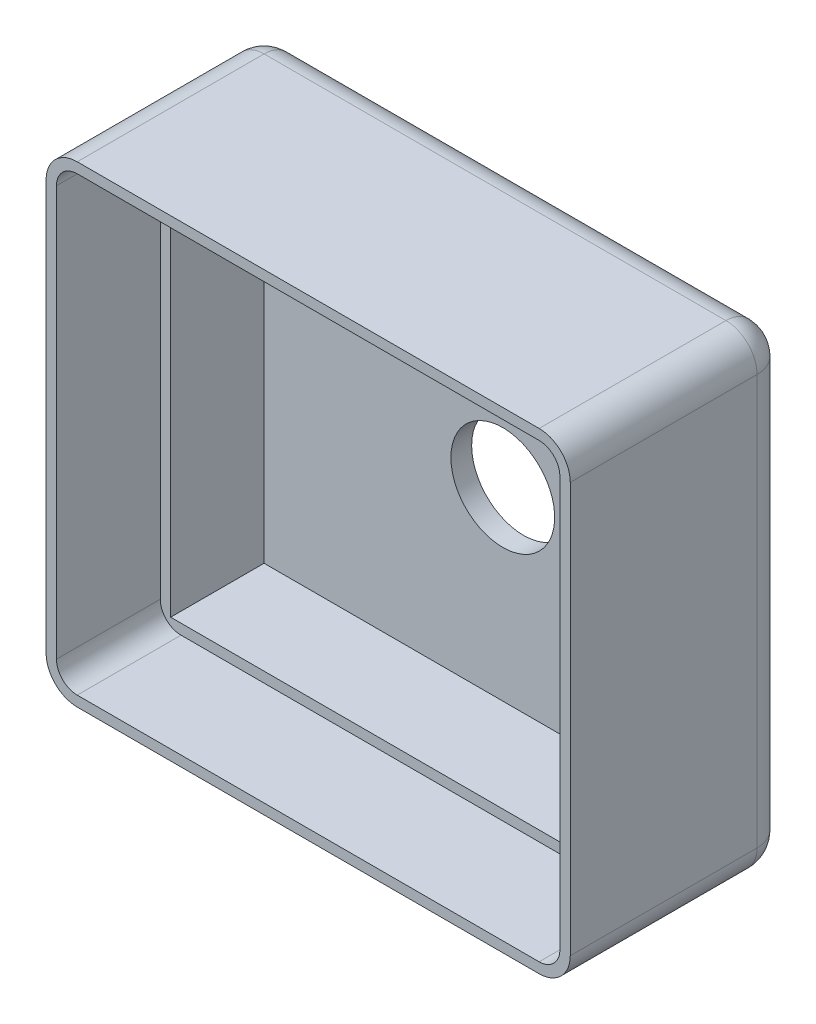
SolidWorks part; units mm, degrees
ref_plane "Piano frontale" through (0, 0, 0) normal (0, 0, 1) x (1, 0, 0)
ref_plane "Piano superiore" through (0, 0, 0) normal (0, 1, 0) x (1, 0, 0)
ref_plane "Piano destro" through (0, 0, 0) normal (1, 0, 0) x (0, 0, -1)
sketch "Schizzo1" plane through (0, 0, 0) normal (0, 0, 1) x (1, 0, 0)
  line L1 (0, 0) -> (50.5, 0)
  line L2 (0, 0) -> (0, 45.5)
  line L3 (0, 45.5) -> (50.5, 45.5)
  line L4 (50.5, 0) -> (50.5, 45.5)
  dimension "D1" = 50.5
  dimension "D2" = 45.5
extrude "Estrusione-Estrusione1" add sketch "Schizzo1" along normal blind 2
sketch "Schizzo5" plane through (0, 0, 2) normal (0, 0, 1) x (1, 0, 0)
  line L0 (0, 0) -> (50.5, 0) construction
  line L1 (50.5, 45.5) -> (48.5, 45.5)
  line L2 (50.5, 45.5) -> (50.5, 0)
  line L3 (50.5, 0) -> (48.5, 0)
  line L4 (48.5, 45.5) -> (48.5, 0)
  dimension "D1" = 2
extrude "Estrusione-Estrusione2" add sketch "Schizzo5" along normal blind 9
sketch "Schizzo6" plane through (0, 0, 2) normal (0, 0, 1) x (1, 0, 0)
  line L0 (0, 45.5) -> (0, 0) construction
  line L1 (48.5, 45.5) -> (0, 45.5)
  line L2 (48.5, 45.5) -> (48.5, 43.5)
  line L3 (48.5, 43.5) -> (0, 43.5)
  line L4 (0, 45.5) -> (0, 43.5)
  dimension "D1" = 2
extrude "Estrusione-Estrusione3" add sketch "Schizzo6" along normal blind 9
sketch "Schizzo7" plane through (0, 0, 2) normal (0, 0, 1) x (1, 0, 0)
  line L0 (0, 0) -> (48.5, 0) construction
  line L1 (0, 43.5) -> (2, 43.5)
  line L2 (0, 43.5) -> (0, 0)
  line L3 (0, 0) -> (2, 0)
  line L4 (2, 43.5) -> (2, 0)
  dimension "D1" = 2
extrude "Estrusione-Estrusione4" add sketch "Schizzo7" along normal blind 9
sketch "Schizzo8" plane through (0, 0, 2) normal (0, 0, 1) x (1, 0, 0)
  line L0 (2, 0) -> (2, 43.5) construction
  line L1 (48.5, 0) -> (2, 0)
  line L2 (48.5, 0) -> (48.5, 2)
  line L3 (48.5, 2) -> (2, 2)
  line L4 (2, 0) -> (2, 2)
  dimension "D1" = 2
extrude "Estrusione-Estrusione5" add sketch "Schizzo8" along normal blind 9
sketch "Schizzo9" plane through (0, 0, 11) normal (0, 0, 1) x (1, 0, 0)
  line L0 (0, 0) -> (50.5, 0) construction
  line L1 (50.5, 45.5) -> (49.5, 45.5)
  line L2 (50.5, 45.5) -> (50.5, 0)
  line L3 (50.5, 0) -> (49.5, 0)
  line L4 (49.5, 45.5) -> (49.5, 0)
  dimension "D1" = 1
extrude "Estrusione-Estrusione6" add sketch "Schizzo9" along normal blind 10
sketch "Schizzo10" plane through (0, 0, 11) normal (0, 0, 1) x (1, 0, 0)
  line L0 (0, 45.5) -> (0, 0) construction
  line L1 (49.5, 0) -> (0, 0)
  line L2 (49.5, 0) -> (49.5, 1)
  line L3 (49.5, 1) -> (0, 1)
  line L4 (0, 0) -> (0, 1)
  dimension "D1" = 1
extrude "Estrusione-Estrusione7" add sketch "Schizzo10" along normal blind 10
sketch "Schizzo11" plane through (0, 0, 11) normal (0, 0, 1) x (1, 0, 0)
  line L0 (49.5, 45.5) -> (0, 45.5) construction
  line L1 (0, 1) -> (1, 1)
  line L2 (0, 1) -> (0, 45.5)
  line L3 (0, 45.5) -> (1, 45.5)
  line L4 (1, 1) -> (1, 45.5)
  dimension "D1" = 1
extrude "Estrusione-Estrusione8" add sketch "Schizzo11" along normal blind 10
sketch "Schizzo12" plane through (0, 0, 11) normal (0, 0, 1) x (1, 0, 0)
  line L0 (49.5, 45.5) -> (49.5, 1) construction
  line L1 (1, 45.5) -> (49.5, 45.5)
  line L2 (1, 45.5) -> (1, 44.5)
  line L3 (1, 44.5) -> (49.5, 44.5)
  line L4 (49.5, 45.5) -> (49.5, 44.5)
  dimension "D1" = 1
extrude "Estrusione-Estrusione9" add sketch "Schizzo12" along normal blind 10
fillet "Raccordo1" radius 3 8 edges at (25.25, 45.5, 0) (0, 45.5, 10.5) (50.5, 45.5, 10.5) (50.5, 0, 10.5) (50.5, 22.75, 0) (25.25, 0, 0) (0, 0, 10.5) (0, 22.75, 0)
sketch "Schizzo13" plane through (0, 0, 0) normal (0, 0, -1) x (-1, 0, 0)
  circle A0 centre (-25, 19.8241) radius 5
  dimension "D1" = 10
extrude "Taglio-Estrusione2" cut sketch "Schizzo13" against normal blind 2
fillet "Raccordo2" radius 2 4 edges at (49.5, 44.5, 16) (49.5, 1, 16) (1, 1, 16) (1, 44.5, 16)
